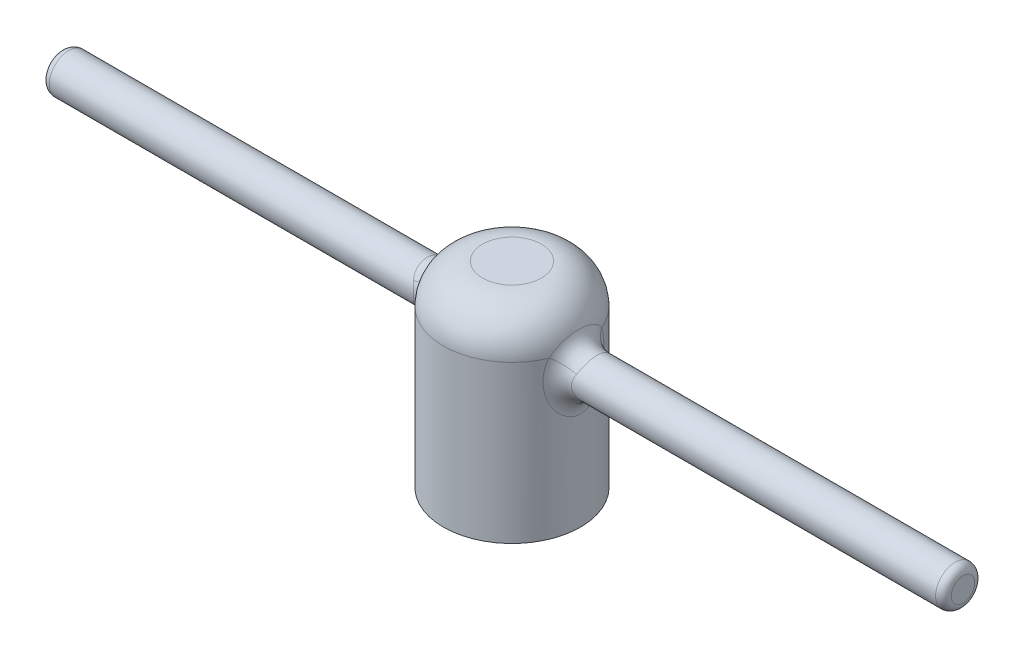
SolidWorks part; units mm, degrees
ref_plane "Front Plane" through (0, 0, 0) normal (0, 0, 1) x (1, 0, 0)
ref_plane "Top Plane" through (0, 0, 0) normal (0, 1, 0) x (1, 0, 0)
ref_plane "Right Plane" through (0, 0, 0) normal (1, 0, 0) x (0, 0, -1)
sketch "Sketch1" plane through (0, 0, 0) normal (0, 1, 0) x (1, 0, 0)
  circle A0 centre (0, 0) radius 17.5
  dimension "D1" = 35
extrude "Boss-Extrude1" add sketch "Sketch1" along normal blind 50
fillet "Fillet1" radius 10 1 edges at (0, 50, 17.5)
sketch "Sketch2" plane through (0, 0, 0) normal (1, 0, 0) x (0, 0, -1)
  line L0 (0, 19.25) -> (0, -19.25) construction
  line L1 (-17.5, 40) -> (17.5, 40) construction
  circle A0 centre (0, 35) radius 5
  dimension "D1" = 10
extrude "Boss-Extrude2" add sketch "Sketch2" along normal mid plane 230
fillet "Fillet2" radius 5 2 edges at (-17.4754, 30.0867, 0.9269) (17.4754, 30.0867, -0.9269)
fillet "Fillet3" radius 2 2 edges at (-115, 35, -5) (115, 35, -5)
hole_wizard "M16 Tapped Hole1" positions "3DSketch3" profile "Sketch6" tap size "M16" standard "ISO"
sketch3d "3DSketch3"
  point P0 (0, 0, 0)
  dimension "D1" = 0
sketch "Sketch6" plane through (0, 0, 0) normal (1, 0, 0) x (0, 0, -1)
  line L0 (0, 0) -> (0, 29.206)
  line L1 (0, 29.206) -> (7, 25)
  line L2 (7, 25) -> (7, 1.025)
  line L3 (7, 1.025) -> (8.025, 0)
  line L5 (8.025, 0) -> (0, 0)
  line L6 (-7, 1.025) -> (-8.025, 0) construction
  line L10 (0, 29.206) -> (-7, 25) construction
  line L11 (0, -6.35) -> (0, 107.95) construction
  dimension "Tap Drill Dia." = 14
  dimension "Tap Drill Depth" = 25
  dimension "Near C'Sink Dia." = 16.05
  dimension "Near C'Sink Angle" = 90
  dimension "Drill Angle" = 118
